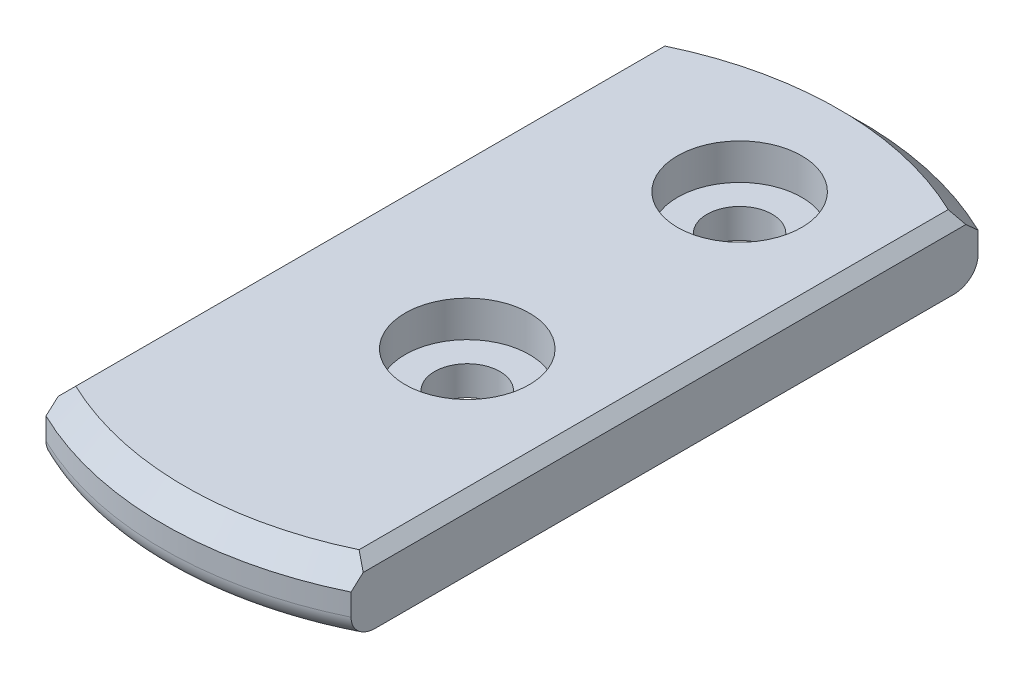
SolidWorks part; units mm, degrees
ref_plane "Front Plane" through (0, 0, 0) normal (0, 0, 1) x (1, 0, 0)
ref_plane "Top Plane" through (0, 0, 0) normal (0, 1, 0) x (1, 0, 0)
ref_plane "Right Plane" through (0, 0, 0) normal (1, 0, 0) x (0, 0, -1)
sketch "Sketch2" plane through (0, 0, 0) normal (0, 1, 0) x (1, 0, 0)
  circle A0 centre (0, 0) radius 16
  dimension "D1" = 32
extrude "Boss-Extrude1" add sketch "Sketch2" along normal blind 3
sketch "Sketch1" plane through (0, 0, 0) normal (0, 1, 0) x (1, 0, 0)
  line L1 (-16, 16) -> (-7, 16)
  line L2 (-16, 16) -> (-16, -16)
  line L3 (-16, -16) -> (-7, -16)
  line L4 (-7, 16) -> (-7, -16)
  line L5 (16, 16) -> (7, 16)
  line L6 (16, 16) -> (16, -16)
  line L7 (16, -16) -> (7, -16)
  line L8 (7, 16) -> (7, -16)
  circle A0 centre (0, 0) radius 16 construction
  dimension "D1" = 32
  dimension "D2" = 7
extrude "Cut-Extrude1" cut sketch "Sketch1" along normal through all
sketch "Sketch3" plane through (0, 3, 0) normal (0, 1, 0) x (1, 0, 0)
  line L0 (7, 14.3875) -> (7, -14.3875) construction
  circle A0 centre (1, 9.4472) radius 1.5
  circle A1 centre (1, -3.0528) radius 1.5
  dimension "D4" = 3
  dimension "D1" = 6
  dimension "D2" = 9.4472
  dimension "D3" = 12.5
extrude "Cut-Extrude2" cut sketch "Sketch3" against normal through all
sketch "Sketch4" plane through (0, 3, 0) normal (0, 1, 0) x (1, 0, 0)
  circle A0 centre (1, 9.4472) radius 2.85
  circle A1 centre (1, -3.0528) radius 2.85
  dimension "D1" = 5.7
extrude "Cut-Extrude3" cut sketch "Sketch4" against normal blind 1.65
chamfer "Chamfer1" distance 0.5 angle 45 2 edges at (-7, 3, 0) (7, 3, 0)
fillet "Fillet1" radius 1 2 edges at (0, 0, -16) (0, 0, 16)
chamfer "Chamfer2" distance 1 angle 45 2 edges at (0, 3, 16) (0, 3, -16)
